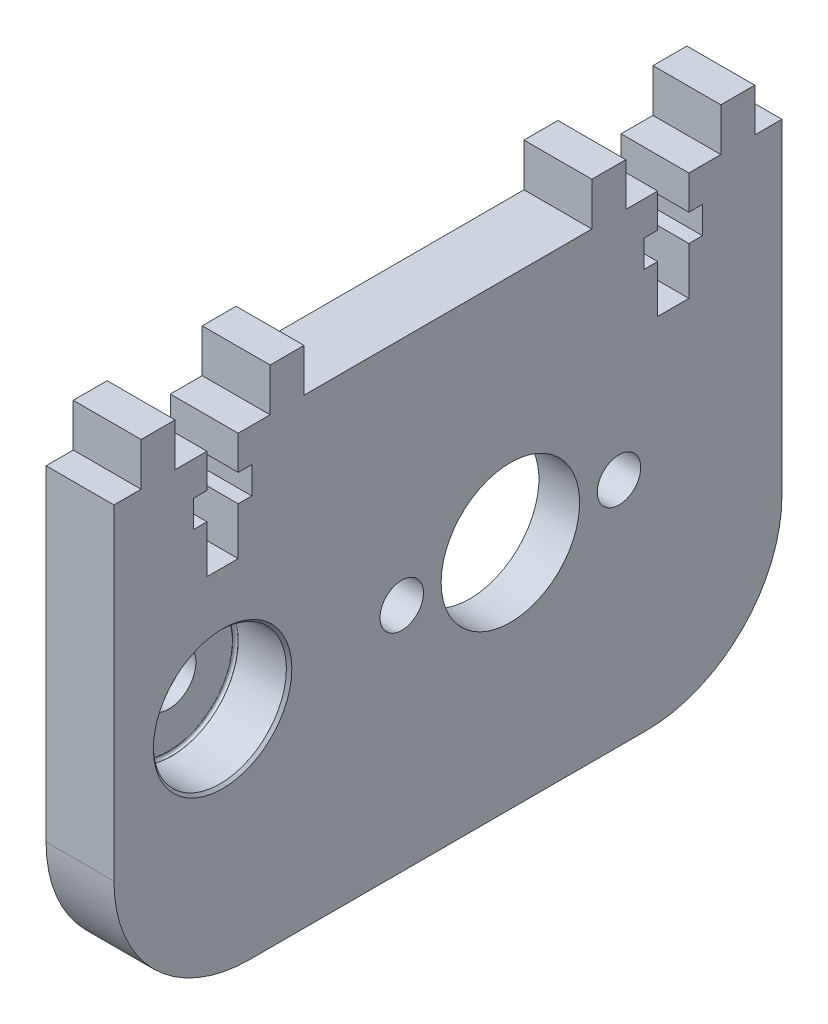
SolidWorks part; units mm, degrees
ref_plane "Front Plane" through (0, 0, 0) normal (0, 0, 1) x (1, 0, 0)
ref_plane "Top Plane" through (0, 0, 0) normal (0, 1, 0) x (1, 0, 0)
ref_plane "Right Plane" through (0, 0, 0) normal (1, 0, 0) x (0, 0, -1)
sketch "Sketch1" plane through (0, 0, 0) normal (1, 0, 0) x (0, 0, -1)
  line L0 (-4.6, 17) -> (-4.6, -17) construction
  line L1 (-29.2, 17) -> (20, 17) construction
  line L2 (-29.2, 17) -> (-29.2, -17)
  line L3 (-29.2, -17) -> (20, -17)
  line L4 (20, 17) -> (20, -17)
  line L5 (-15.2, 17) -> (-17.7, 17) construction
  line L6 (-15.2, 17) -> (-15.2, 20.175)
  line L7 (-15.2, 20.175) -> (-17.7, 20.175)
  line L8 (-17.7, 17) -> (-17.7, 20.175)
  line L9 (-24.7, 17) -> (-27.2, 17) construction
  line L10 (-24.7, 17) -> (-24.7, 20.175)
  line L11 (-24.7, 20.175) -> (-27.2, 20.175)
  line L12 (-27.2, 17) -> (-27.2, 20.175)
  line L13 (-27.2, 17) -> (-29.2, 17)
  line L14 (-17.7, 17) -> (-24.7, 17) construction
  line L15 (-20.05, 17) -> (-17.7, 17)
  line L16 (-20.05, 17) -> (-22.35, 17) construction
  line L17 (-20.05, 17) -> (-20.05, 14.5)
  line L18 (-20.05, 9) -> (-22.35, 9)
  line L19 (-22.35, 17) -> (-22.35, 14.5)
  line L20 (-19.05, 14.5) -> (-20.05, 14.5)
  line L21 (-19.05, 14.5) -> (-19.05, 12.5)
  line L22 (-19.05, 12.5) -> (-20.05, 12.5)
  line L23 (-23.35, 14.5) -> (-23.35, 12.5)
  line L24 (-22.35, 17) -> (-24.7, 17)
  line L25 (-22.35, 14.5) -> (-23.35, 14.5)
  line L26 (-22.35, 12.5) -> (-23.35, 12.5)
  line L27 (-20.05, 12.5) -> (-20.05, 9)
  line L28 (-22.35, 12.5) -> (-22.35, 9)
  line L29 (18, 17) -> (20, 17)
  line L30 (10.85, 17) -> (13.15, 17) construction
  line L31 (8.5, 17) -> (15.5, 17) construction
  line L32 (15.5, 17) -> (18, 17) construction
  line L33 (6, 17) -> (8.5, 17) construction
  line L34 (13.15, 12.5) -> (13.15, 9)
  line L35 (10.85, 12.5) -> (10.85, 9)
  line L36 (13.15, 12.5) -> (14.15, 12.5)
  line L37 (13.15, 14.5) -> (14.15, 14.5)
  line L38 (13.15, 17) -> (15.5, 17)
  line L39 (14.15, 14.5) -> (14.15, 12.5)
  line L40 (9.85, 12.5) -> (10.85, 12.5)
  line L41 (9.85, 14.5) -> (9.85, 12.5)
  line L42 (9.85, 14.5) -> (10.85, 14.5)
  line L43 (13.15, 17) -> (13.15, 14.5)
  line L44 (10.85, 9) -> (13.15, 9)
  line L45 (10.85, 17) -> (10.85, 14.5)
  line L46 (10.85, 17) -> (8.5, 17)
  line L47 (18, 17) -> (18, 20.175)
  line L48 (15.5, 20.175) -> (18, 20.175)
  line L49 (15.5, 17) -> (15.5, 20.175)
  line L50 (8.5, 17) -> (8.5, 20.175)
  line L51 (6, 20.175) -> (8.5, 20.175)
  line L52 (6, 17) -> (6, 20.175)
  line L53 (-15.2, 17) -> (6, 17)
  circle A0 centre (0, 0) radius 14.5 construction
  circle A1 centre (-21.2, 0) radius 4.7625 construction
  circle A2 centre (-21.2, 0) radius 1.5875 construction
  point P7 (20, 0)
  point P30 (-21.2, 17)
  point P31 (-21.2, 9)
  dimension "D1" = 29
  dimension "D2" = 21.2
  dimension "D3" = 9.525
  dimension "D4" = 3.175
  dimension "D5" = 20
  dimension "D6" = 8
  dimension "D7" = 17
  dimension "D8" = 2
  dimension "D9" = 2.5
  dimension "D10" = 2.3
  dimension "D11" = 2
  dimension "D12" = 4.3
  dimension "D13" = 8
  dimension "D14" = 2.5
  dimension "D15" = 3.175
  dimension "D16" = 7
extrude "Boss-Extrude1" add sketch "Sketch1" along normal blind 5
sketch "Sketch2" plane through (0, 0, 0) normal (-1, 0, 0) x (0, 0, 1)
  circle A0 centre (0, 0) radius 13.95
  dimension "D1" = 27.9
extrude "Cut-Extrude1" cut sketch "Sketch2" against normal blind 2
sketch "Sketch3" plane through (5, 0, 0) normal (1, 0, 0) x (0, 0, -1)
  circle A0 centre (-21.2, 0) radius 4.9
  dimension "D1" = 9.8
extrude "Cut-Extrude2" cut sketch "Sketch3" against normal blind 3.9624
sketch "Sketch4" plane through (2, 0, 0) normal (-1, 0, 0) x (0, 0, 1)
  line L0 (0, 14.5) -> (0, -14.5) construction
  circle A0 centre (-8, 0) radius 1.6
  circle A1 centre (0, 0) radius 14.5 construction
  circle A2 centre (8, 0) radius 1.6
  circle A3 centre (0, 0) radius 5.1
  dimension "D1" = 3.2
  dimension "D2" = 8
  dimension "D3" = 10.2
extrude "Cut-Extrude3" cut sketch "Sketch4" against normal up to next
sketch "Sketch5" plane through (1.0376, 0, 0) normal (1, 0, 0) x (0, 0, -1)
  circle A0 centre (-21.2, 0) radius 2
  dimension "D1" = 4
extrude "Cut-Extrude4" cut sketch "Sketch5" against normal through all
fillet "Fillet1" radius 10 2 edges at (2.5, -17, -20) (2.5, -17, 29.2)
sketch "Sketch6" plane through (0, 0, 0) normal (-1, 0, 0) x (0, 0, 1)
  line L0 (-5, -13.0232) -> (-5, -17)
  line L1 (19.2, -17) -> (-10, -17) construction
  line L2 (-5, -17) -> (5, -17)
  line L3 (5, -17) -> (5, -13.0232)
  arc A0 (-5, -13.0232) -> (5, -13.0232) centre (0, 0) ccw
  circle A1 centre (0, 0) radius 13.95 construction
  point P9 (0, -17)
  dimension "D1" = 10
extrude "Boss-Extrude2" add sketch "Sketch6" along normal blind 4
fillet "Fillet2" radius 1 5 edges at (-2, -13.0232, 5) (-2, -13.0232, -5) (-4, -17, 0) (-2, -17, 5) (-2, -17, -5)
chamfer "Chamfer1" distance 0.2 angle 45 1 edges at (5, 0, 16.3)
ref_axis "Axis1" through (5, 0, 0) along (-1, 0, 0)
sketch "Sketch7" plane through (0, 0, 0) normal (0, 1, 0) x (1, 0, 0)
  line L0 (5, 0) -> (2, 0) construction
  line L1 (2, -6.4) -> (2, -9.6) construction
  circle A0 centre (1.9, -13.85) radius 0.15
  dimension "D1" = 0.3
  dimension "D2" = 13.85
  dimension "D3" = 0.1
revolve "Cut-Revolve1" cut sketch "Sketch7" angle 360 about axis through (5, 0, 0) along (-1, 0, 0)
ref_axis "Axis2" through (0, 0, 21.2) along (1, 0, 0)
sketch "Sketch10" plane through (0, 0, 0) normal (0, 1, 0) x (1, 0, 0)
  line L0 (0, -21.2) -> (1.0376, -21.2) construction
  line L1 (1.0376, -23.2) -> (1.0376, -19.2) construction
  circle A0 centre (1.1376, -16.4) radius 0.15
  dimension "D1" = 4.8
  dimension "D2" = 0.3
  dimension "D3" = 0.1
revolve "Cut-Revolve2" cut sketch "Sketch10" angle 360 about axis through (0, 0, 21.2) along (1, 0, 0)
